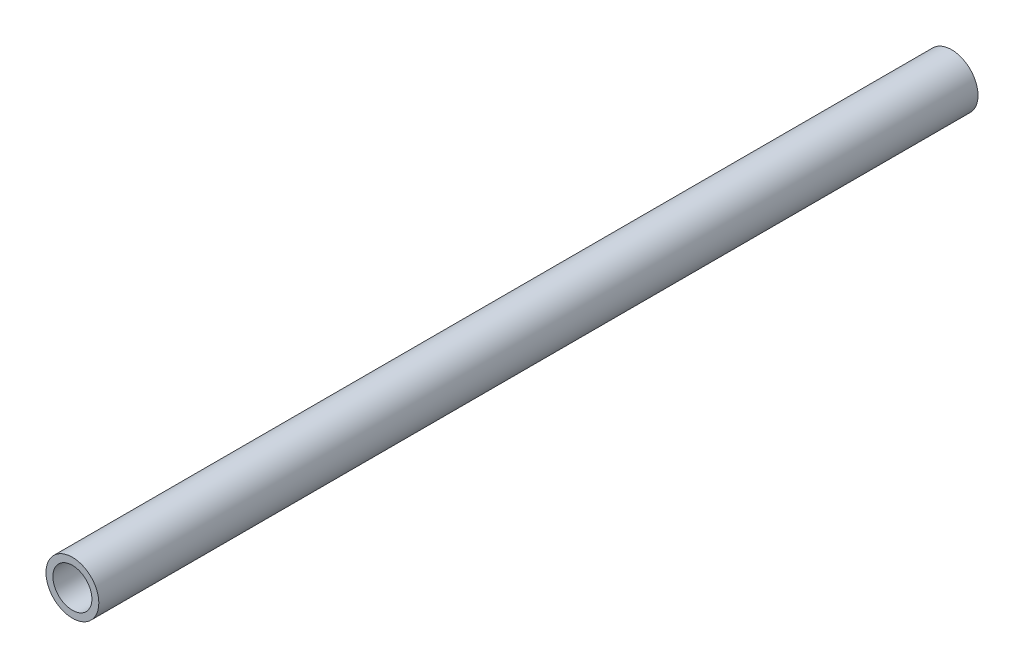
SolidWorks part; units mm, degrees
material "AISI 1020"
ref_plane "Plan de face" through (0, 0, 0) normal (0, 0, 1) x (1, 0, 0)
ref_plane "Plan de dessus" through (0, 0, 0) normal (0, 1, 0) x (1, 0, 0)
ref_plane "Plan de droite" through (0, 0, 0) normal (1, 0, 0) x (0, 0, -1)
sketch "Esquisse1" plane through (0, 0, 0) normal (0, 0, 1) x (1, 0, 0)
  circle A0 centre (0, 0) radius 4.57
  circle A1 centre (0, 0) radius 3.37
  dimension "D1" = 9.14
  dimension "D2" = 1.2
extrude "Boss.-Extru.1" add sketch "Esquisse1" along normal blind 152
sketch "Esquisse2" plane through (0, 0, 152) normal (0, 0, 1) x (1, 0, 0)
  circle A0 centre (0, 0) radius 4
  dimension "D1" = 8
extrude "Boss.-Extru.2" [suppressed] add sketch "Esquisse2" along normal blind 149.1
